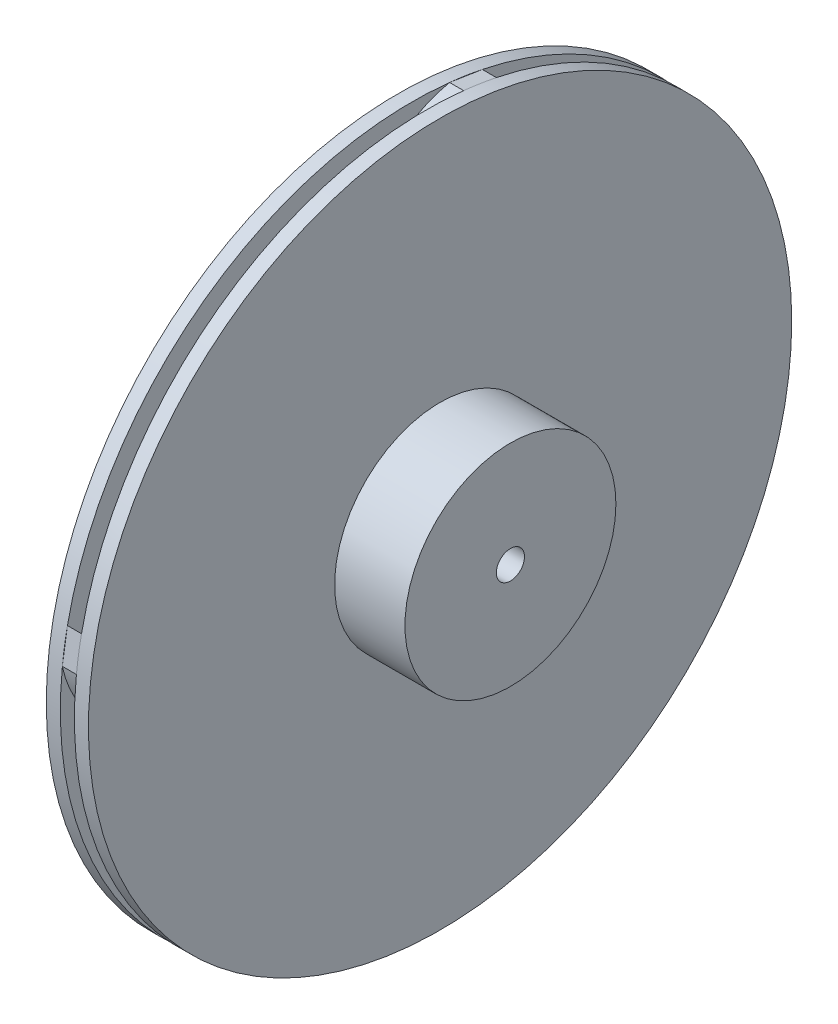
SolidWorks part; units mm, degrees
ref_plane "Front Plane" through (0, 0, 0) normal (0, 0, 1) x (1, 0, 0)
ref_plane "Top Plane" through (0, 0, 0) normal (0, 1, 0) x (1, 0, 0)
ref_plane "Right Plane" through (0, 0, 0) normal (1, 0, 0) x (0, 0, -1)
sketch "Sketch1" plane through (0, 0, 0) normal (1, 0, 0) x (0, 0, -1)
  circle A0 centre (0, 0) radius 5 construction
  circle A1 centre (0, 0) radius 25 construction
  spline S0 degree 3 poles (0, 5) (4.4975, 10.7345) (18.0773, 8.4044) (22.9032, -1.3715) (24.4949, -5) knots 0 0 0 0 0.618778 1 1 1 1
  spline S1 degree 3 poles (-1.493, 4.7719) (-1.3344, 6.9234) (1.5164, 9.3758) (6.9225, 11.0632) (12.6682, 10.3229) (18.6305, 7.1656) (22.3919, 2.3509) (24.5506, -1.105) (24.8567, -2.673) knots 0 0 0 0 0.172506 0.296265 0.482617 0.652804 0.864379 1 1 1 1
  spline S2 degree 1 poles (-1.493, 4.7719) (0, 5) knots 0 0 1 1
  spline S3 degree 1 poles (24.4949, -5) (24.8567, -2.673) knots 0 0 1 1
  spline S4 degree 3 poles (4.7719, 1.493) (6.9234, 1.3344) (9.3758, -1.5164) (11.0632, -6.9225) (10.3229, -12.6682) (7.1656, -18.6305) (2.3509, -22.3919) (-1.105, -24.5506) (-2.673, -24.8567) knots 0 0 0 0 0.172506 0.296265 0.482617 0.652804 0.864379 1 1 1 1
  spline S5 degree 3 poles (5, 0) (10.7345, -4.4975) (8.4044, -18.0773) (-1.3715, -22.9032) (-5, -24.4949) knots 0 0 0 0 0.618778 1 1 1 1
  spline S6 degree 1 poles (-5, -24.4949) (-2.673, -24.8567) knots 0 0 1 1
  spline S7 degree 1 poles (4.7719, 1.493) (5, 0) knots 0 0 1 1
  spline S8 degree 3 poles (1.493, -4.7719) (1.3344, -6.9234) (-1.5164, -9.3758) (-6.9225, -11.0632) (-12.6682, -10.3229) (-18.6305, -7.1656) (-22.3919, -2.3509) (-24.5506, 1.105) (-24.8567, 2.673) knots 0 0 0 0 0.172506 0.296265 0.482617 0.652804 0.864379 1 1 1 1
  spline S9 degree 3 poles (0, -5) (-4.4975, -10.7345) (-18.0773, -8.4044) (-22.9032, 1.3715) (-24.4949, 5) knots 0 0 0 0 0.618778 1 1 1 1
  spline S10 degree 1 poles (-24.4949, 5) (-24.8567, 2.673) knots 0 0 1 1
  spline S11 degree 1 poles (1.493, -4.7719) (0, -5) knots 0 0 1 1
  spline S12 degree 3 poles (-4.7719, -1.493) (-6.9234, -1.3344) (-9.3758, 1.5164) (-11.0632, 6.9225) (-10.3229, 12.6682) (-7.1656, 18.6305) (-2.3509, 22.3919) (1.105, 24.5506) (2.673, 24.8567) knots 0 0 0 0 0.172506 0.296265 0.482617 0.652804 0.864379 1 1 1 1
  spline S13 degree 3 poles (-5, 0) (-10.7345, 4.4975) (-8.4044, 18.0773) (1.3715, 22.9032) (5, 24.4949) knots 0 0 0 0 0.618778 1 1 1 1
  spline S14 degree 1 poles (5, 24.4949) (2.673, 24.8567) knots 0 0 1 1
  spline S15 degree 1 poles (-4.7719, -1.493) (-5, 0) knots 0 0 1 1
  point P47 (0, 0)
  point P64 (0, 0)
  dimension "D1" = 50
  dimension "D2" = 10
extrude "Boss-Extrude1" add sketch "Sketch1" along normal blind 1
sketch "Sketch2" plane through (1, 0, 0) normal (1, 0, 0) x (0, 0, -1)
  circle A0 centre (0, 0) radius 5
  circle A1 centre (0, 0) radius 25
extrude "Boss-Extrude2" add sketch "Sketch2" along normal blind 1
extrude "Boss-Extrude6" add sketch "Sketch2<4>" against normal blind 1 from surface starting at face at (0, 0.5247, -11.9646)
sketch "Sketch2<4>" plane through (1, 0, 0) normal (1, 0, 0) x (0, 0, -1) same geometry as "Sketch2"
sketch "Sketch3" plane through (2, 0, 0) normal (1, 0, 0) x (0, 0, -1)
  circle A0 centre (0, 0) radius 7.5
  dimension "D1" = 15
extrude "Boss-Extrude7" add sketch "Sketch3" along normal blind 5
sketch "Sketch4" plane through (7, 0, 0) normal (1, 0, 0) x (0, 0, -1)
  circle A0 centre (0, 0) radius 1
  dimension "D1" = 2
extrude "Cut-Extrude1" cut sketch "Sketch4" against normal blind 4
